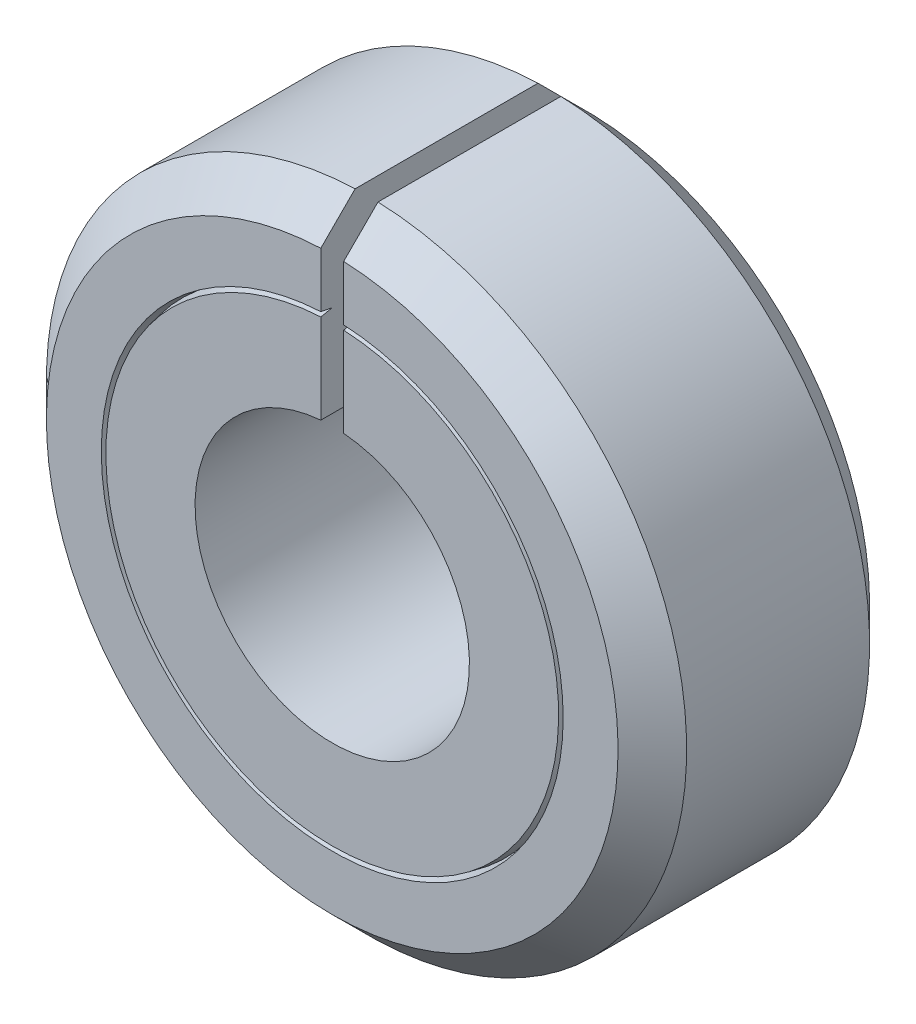
SolidWorks part; units mm, degrees
ref_plane "Front Plane" through (0, 0, 0) normal (0, 0, 1) x (1, 0, 0)
ref_plane "Top Plane" through (0, 0, 0) normal (0, 1, 0) x (1, 0, 0)
ref_plane "Right Plane" through (0, 0, 0) normal (1, 0, 0) x (0, 0, -1)
sketch "Sketch1" plane through (0, 0, 0) normal (1, 0, 0) x (0, 0, -1)
  line L0 (-10.1123, 0) -> (9.9442, 0) construction
  line L1 (-5.5, 6) -> (5.5, 6)
  line L2 (-5.5, 6) -> (-5.5, 9.9)
  line L3 (-4, 14) -> (4, 14)
  line L4 (5.5, 6) -> (5.5, 9.9)
  line L5 (-5.5, 6) -> (5.5, 14) construction
  line L6 (-5.5, 14) -> (5.5, 6) construction
  line L7 (-5.5, 12.5) -> (-4, 14)
  line L8 (4, 14) -> (5.5, 12.5)
  line L15 (-5.5, 10) -> (5, 10) construction
  line L16 (5.5, 10.1) -> (5, 10)
  line L17 (5, 10) -> (5.5, 9.9)
  line L18 (-5.5, 10.1) -> (-5, 10)
  line L19 (-5, 10) -> (-5.5, 9.9)
  line L20 (-5.5, 10.1) -> (-5.5, 12.5)
  line L21 (5.5, 10.1) -> (5.5, 12.5)
  point P0 (0, 10)
  point P12 (0, 10)
  dimension "D1" = 8
  dimension "D2" = 11
  dimension "D3" = 10
  dimension "D4" = 0.1
  dimension "D5" = 0.1
  dimension "D6" = 0.1
  dimension "D7" = 0.1
  dimension "D10" = 0.5
  dimension "D11" = 0.5
revolve "Revolve1" add sketch "Sketch1" angle 360 about L0 region at (0, 9.9081, 0)
sketch "Sketch3" plane through (0, 0, 0) normal (0, 0, 1) x (1, 0, 0)
  line L1 (-0.5, 14) -> (0.5, 14)
  line L2 (-0.5, 14) -> (-0.5, 0)
  line L3 (-0.5, 0) -> (0.5, 0)
  line L4 (0.5, 14) -> (0.5, 0)
  line L5 (-0.5, 14) -> (0.5, 0) construction
  line L6 (-0.5, 0) -> (0.5, 14) construction
  point P0 (0, 7)
  dimension "D1" = 1
  dimension "D2" = 14
extrude "Cut-Extrude2" cut sketch "Sketch3" against normal mid plane 30
